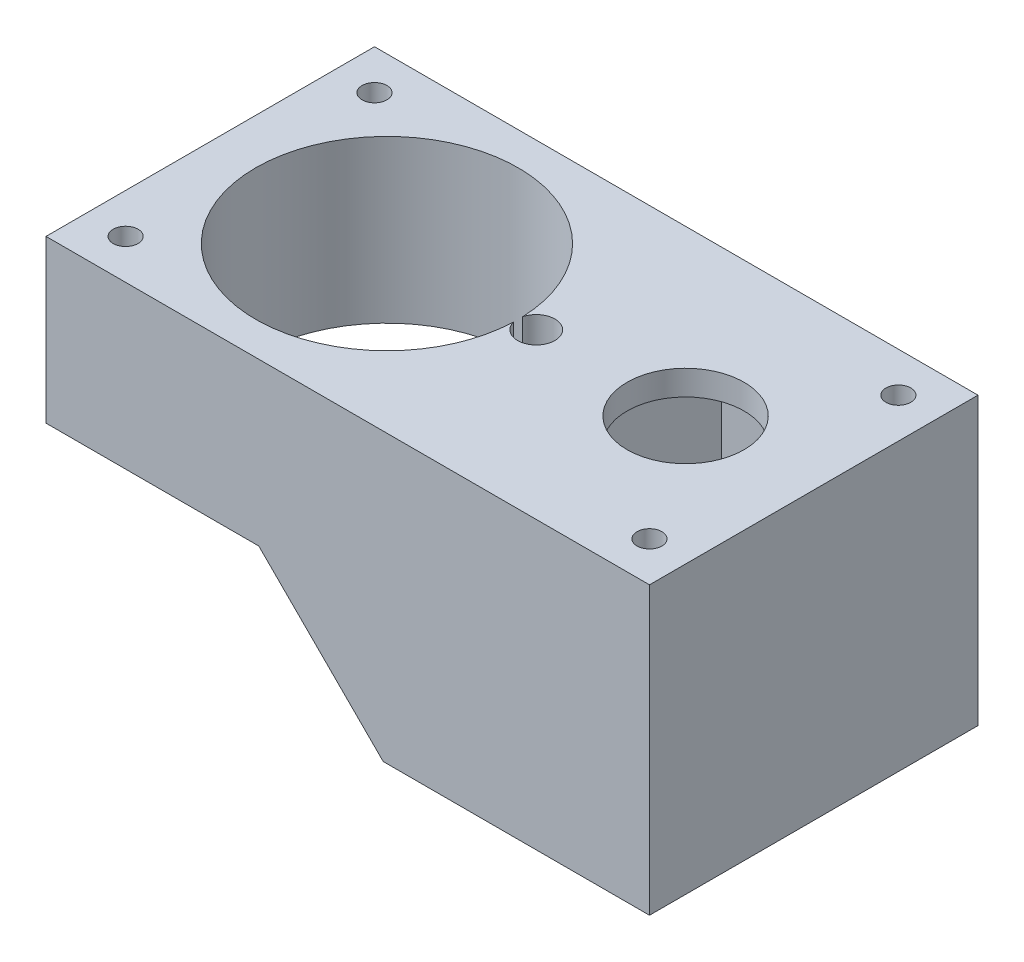
SolidWorks part; units mm, degrees
ref_plane "Plan de face" through (0, 0, 0) normal (0, 0, 1) x (1, 0, 0)
ref_plane "Plan de dessus" through (0, 0, 0) normal (0, 1, 0) x (1, 0, 0)
ref_plane "Plan de droite" through (0, 0, 0) normal (1, 0, 0) x (0, 0, -1)
sketch "Esquisse1" plane through (0, 0, 0) normal (0, 1, 0) x (1, 0, 0)
  line L0 (0, 5.5) -> (22.05, 5.5) construction
  line L1 (0, 0) -> (22.05, 0) construction
  line L2 (0, 0) -> (0, 11) construction
  line L3 (0, 11) -> (22.05, 11) construction
  line L4 (22.05, 0) -> (22.05, 11) construction
  line L5 (22.05, 11) -> (13.95, 0) construction
  line L6 (13.95, 0) -> (13.95, 11) construction
  line L7 (16.45, 11) -> (13.95, 8.5) construction
  line L8 (16.45, 0) -> (16.45, 11) construction
  line L10 (13.95, 2.5) -> (16.45, 0) construction
  circle A0 centre (6, 5.5) radius 5 construction
  circle A1 centre (12, 5.5) radius 5 construction
  circle A2 centre (18, 5.5) radius 1.25 construction
  point P14 (1, 5.5)
  dimension "D1" = 10
  dimension "D3" = 2.5
  dimension "D2" = 6
  dimension "D4" = 6
  dimension "D5" = 1
  dimension "D6" = 11
  dimension "D7" = 8.1
  dimension "D8" = 2.5
sketch "Esquisse2" plane through (0, 0, 0) normal (0, 1, 0) x (1, 0, 0)
  line L0 (11.025, 11) -> (11.025, 12.1) construction
  line L1 (0, 11) -> (22.05, 11)
  line L2 (0, 11) -> (0, 0)
  line L3 (0, 0) -> (22.05, 0)
  line L4 (22.05, 11) -> (22.05, 0)
  line L5 (-1.1, 12.1) -> (23.15, 12.1)
  line L6 (-1.1, 12.1) -> (-1.1, -1.1)
  line L7 (-1.1, -1.1) -> (23.15, -1.1)
  line L8 (23.15, 12.1) -> (23.15, -1.1)
  line L9 (0, 2.5) -> (2.5, 0)
  line L10 (-1.1, 5.5) -> (0, 5.5) construction
  line L12 (22.05, 8.5) -> (19.55, 11)
  line L13 (19.55, 11) -> (19.55, 0) construction
  line L14 (19.55, 0) -> (22.05, 2.5)
  line L15 (0.5, 0.5) -> (21.55, 0.5) construction
  line L16 (2.5, 11) -> (0, 8.5)
  line L17 (13.95, 11) -> (12.45, 11)
  line L18 (0.5, 0.5) -> (0.5, 10.5) construction
  line L19 (0.5, 10.5) -> (21.55, 10.5) construction
  line L20 (21.55, 0.5) -> (21.55, 10.5) construction
  line L21 (13.95, 11) -> (13.95, 0)
  line L22 (13.95, 0) -> (12.45, 0)
  line L23 (12.45, 11) -> (12.45, 0)
  circle A0 centre (0.5, 0.5) radius 0.5
  circle A1 centre (21.55, 0.5) radius 0.5
  circle A2 centre (21.55, 10.5) radius 0.5
  circle A3 centre (0.5, 10.5) radius 0.5
  dimension "D3" = 1
  dimension "D1" = 1.1
  dimension "D2" = 2.5
  dimension "D4" = 1.5
extrude "Boss.-Extru.1" add sketch "Esquisse2" along normal blind 10.5 contours L9 L2 L3 | L8 L5 L6 L7 L1 L4 L3 L2 | L16 L1 L2 | L12 L4 L1 | L14 L3 L4 | A0 L2 L3 | A3 L1 L2 | A2 L4 L1 | A1 L3 L4 | L21 L17 L23 L22 region at (0.9648, 0, -10.0352) region at (0.1117, 0, -10.8883) region at (0.9648, 0, -0.9648) region at (21.0852, 0, -10.0352) region at (0.1117, 0, -0.1117) region at (21.9383, 0, -10.8883) region at (21.0852, 0, -0.9648) region at (21.9383, 0, -0.1117) region at (11.025, 0, -11.8239)
sketch "Esquisse3" plane through (0, 10.5, 0) normal (0, 1, 0) x (1, 0, 0)
  line L1 (23.15, -1.1) -> (-1.1, -1.1)
  line L2 (23.15, -1.1) -> (23.15, 12.1)
  line L3 (23.15, 12.1) -> (-1.1, 12.1)
  line L4 (-1.1, -1.1) -> (-1.1, 12.1)
  circle A0 centre (6, 5.5) radius 5.275
  circle A1 centre (12, 5.5) radius 0.75
  circle A2 centre (18, 5.5) radius 2.35
  circle A3 centre (21.55, 0.5) radius 0.5 construction
  circle A4 centre (21.55, 10.5) radius 0.5 construction
  circle A5 centre (0.5, 10.5) radius 0.5 construction
  circle A6 centre (0.5, 0.5) radius 0.5 construction
  circle A7 centre (21.55, 0.5) radius 0.5
  circle A8 centre (21.55, 10.5) radius 0.5
  circle A9 centre (0.5, 10.5) radius 0.5
  circle A10 centre (0.5, 0.5) radius 0.5
  line M15 (0, 8.5) -> (2.5, 11)
  line M16 (2.5, 11) -> (12.45, 11)
  line M17 (19.55, 11) -> (22.05, 8.5)
  line M19 (22.05, 2.5) -> (19.55, 0)
  line M20 (19.55, 0) -> (13.95, 0)
  line M21 (2.5, 0) -> (0, 2.5)
  line M22 (0, 2.5) -> (0, 8.5)
  line M23 (23.15, -1.1) -> (23.15, 12.1)
  line M24 (23.15, 12.1) -> (-1.1, 12.1)
  line M25 (-1.1, 12.1) -> (-1.1, -1.1)
  line M26 (-1.1, -1.1) -> (23.15, -1.1)
  circle M27 centre (21.55, 10.5) radius 0.5
  circle M30 centre (21.55, 0.5) radius 0.5
  line M31 (22.05, 8.5) -> (22.05, 2.5)
  circle M34 centre (0.5, 10.5) radius 0.5
  circle M36 centre (0.5, 0.5) radius 0.5
  line M44 (13.95, 0) -> (13.95, 11)
  line M45 (13.95, 11) -> (19.55, 11)
  line M46 (12.45, 11) -> (12.45, 0)
  line M47 (12.45, 0) -> (2.5, 0)
  dimension "D1" = 10.55
  dimension "D2" = 1.5
  dimension "D3" = 4.7
extrude "Boss.-Extru.2" add sketch "Esquisse3" along normal blind 1 contours A1 A0 M46 M16 M15 M22 M21 M47 | A2 M44 M20 M19 M31 M17 M45 | A1 M26 M23 M24 M25 M46 M47 M21 M22 M15 M16 M27 M36 M30 M34 M20 M44 M45 M17 M31 M19 region at (11.025, 10.5, 0.8239) region at (0.5589, 10.5, -5.5) region at (20.7034, 10.5, -9.6534)
sketch "Esquisse4" plane through (0, 0, 1.1) normal (0, 0, 1) x (1, 0, 0)
  line L1 (-1.1, 0) -> (12.45, 0)
  line L2 (-1.1, 0) -> (-1.1, 5)
  line L3 (-1.1, 5) -> (12.45, 5)
  line L4 (12.45, 0) -> (12.45, 5)
  dimension "D1" = 5
extrude "Enlèv. mat.-Extru.1" cut sketch "Esquisse4" against normal through all
chamfer "Chanfrein1" distance 5 angle 45 2 edges at (12.45, 5, -11.55) (12.45, 5, 0.55)
sketch "Esquisse5" plane through (0, 10.5, 0) normal (0, -1, 0) x (1, 0, 0)
  arc A0 (11.2719, -5.32) -> (11.2719, -5.68) centre (6, -5.5) ccw
  arc A1 (11.2719, -5.68) -> (11.2719, -5.32) centre (12, -5.5) ccw
  arc A2 (11.2719, -5.32) -> (11.2719, -5.68) centre (6, -5.5) ccw construction
  arc A3 (12.45, -4.9) -> (11.2719, -5.32) centre (12, -5.5) ccw construction
  arc A5 (11.7998, -6.9361) -> (11.7998, -4.0639) centre (12, -5.5) ccw
  arc A6 (11.7998, -4.0639) -> (11.7998, -6.9361) centre (6, -5.5) ccw
  dimension "D1" = 0.7
  dimension "D2" = 0.7
extrude "Boss.-Extru.3" add sketch "Esquisse5" along normal up to surface (5.5 mm away) up to face at (0.5, 5, 0)
sketch "Esquisse6" plane through (0, 11.5, 0) normal (0, 1, 0) x (1, 0, 0)
  circle A0 centre (12, 5.5) radius 0.75
  arc A1 (12.45, 4.9) -> (12.45, 6.1) centre (12, 5.5) ccw construction
extrude "Enlèv. mat.-Extru.2" cut sketch "Esquisse6" against normal through all
chamfer "Chanfrein2" distance 0.5 angle 45 4 edges at (21.55, 0, 0) (21.55, 0, -10) (0.5, 5, 0) (0.5, 5, -10)
